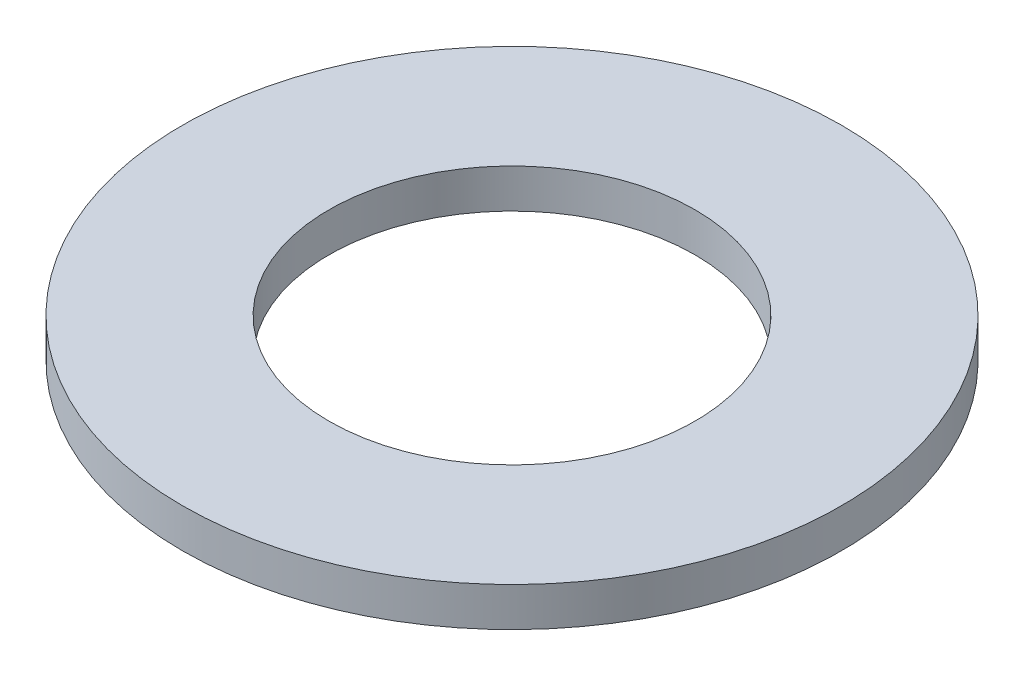
SolidWorks part; units mm, degrees
ref_plane "Front Plane" through (0, 0, 0) normal (0, 0, 1) x (1, 0, 0)
ref_plane "Top Plane" through (0, 0, 0) normal (0, 1, 0) x (1, 0, 0)
ref_plane "Right Plane" through (0, 0, 0) normal (1, 0, 0) x (0, 0, -1)
sketch "Sketch1" plane through (0, 0, 0) normal (0, 1, 0) x (1, 0, 0)
  circle A0 centre (0, 0) radius 67.5
  dimension "FLANGE_OD" = 135
extrude "Boss-Extrude1" add sketch "Sketch1" along normal blind 8
sketch "Sketch2" plane through (0, 0, 0) normal (0, 1, 0) x (1, 0, 0)
  circle A0 centre (0, 0) radius 37.5
  dimension "BORE_D" = 75
extrude "Cut-Extrude1" cut sketch "Sketch2" along normal through all
sketch "Sketch3" plane through (0, 8, 0) normal (0, 1, 0) x (1, 0, 0)
  circle A0 centre (0, 0) radius 22.5853 construction
  circle A1 centre (-22.5853, 0) radius 4.6729
  dimension "BOLT_D" = 9.3457
  dimension "BOLT_PCD" = 45.1706
extrude "Cut-Extrude2" cut sketch "Sketch3" against normal blind 6.0279 rebuild error yes
pattern_circular "CirPattern1" count 6 over 360 rebuild error yes
